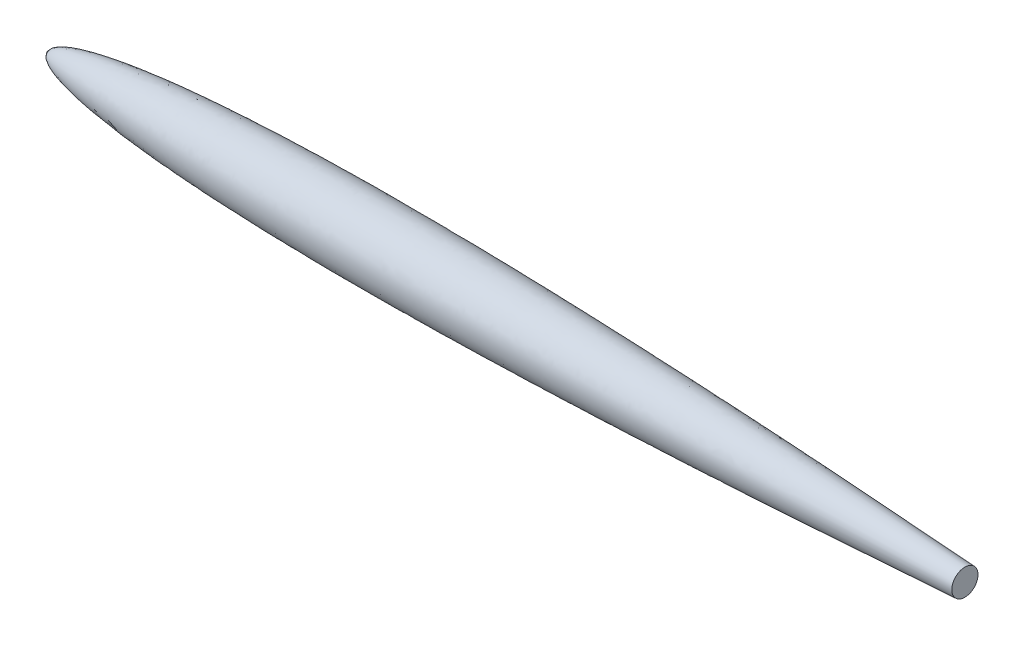
SolidWorks part; units mm, degrees
ref_plane "Front Plane" through (0, 0, 0) normal (0, 0, 1) x (1, 0, 0)
ref_plane "Top Plane" through (0, 0, 0) normal (0, 1, 0) x (1, 0, 0)
ref_plane "Right Plane" through (0, 0, 0) normal (1, 0, 0) x (0, 0, -1)
sketch "rootSketch" plane through (0, 0, 0) normal (0, 1, 0) x (1, 0, 0)
  line L0 (0, 0) -> (12000, 0) construction
  line L1 (2287.5, -274.5) -> (2287.5, 274.5) construction
  line L2 (0, 0) -> (9150, 0)
  spline S0 degree 4 poles (0, 0) (0.0002, 1.1783) (0.1019, 3.5275) (0.5605, 7.0328) (1.7549, 11.5943) (3.4354, 15.9) (5.4991, 19.934) (8.311, 24.4289) (11.4852, 28.5908) (14.9769, 32.5095) (19.9691, 37.4422) (26.9376, 43.4504) (36.0876, 50.0708) (47.4769, 57.0778) (61.5404, 64.6525) (77.1838, 72.0716) (94.7922, 79.4526) (114.338, 86.7678) (138.331, 94.9404) (167.4375, 103.839) (202.1902, 113.2976) (242.6189, 123.0791) (283.8524, 132.0744) (324.9149, 140.2471) (365.7664, 147.7384) (416.4511, 156.3658) (477.0221, 165.7669) (547.8456, 175.6689) (630.5882, 186.0011) (715.1014, 195.4737) (801.3628, 204.1819) (889.3556, 212.1992) (977.4135, 219.4631) (1065.524, 226.0562) (1153.6774, 232.0453) (1241.8663, 237.486) (1352.1845, 243.6614) (1484.6517, 250.1476) (1639.2816, 256.5129) (1816.0804, 262.345) (1992.9164, 266.8975) (2169.7779, 270.3041) (2346.6562, 272.6757) (2523.5444, 274.1064) (2744.6606, 274.8195) (3010.0013, 274.0955) (3319.5538, 271.2162) (3673.2968, 265.5239) (4026.9995, 257.745) (4380.6568, 248.1375) (4734.2663, 236.9143) (5087.8269, 224.2504) (5441.3385, 210.2884) (5794.8011, 195.1423) (6148.2151, 178.9004) (6501.5801, 161.6274) (6810.731, 145.6485) (7075.6854, 131.3482) (7296.4585, 119.0291) (7473.0634, 108.9317) (7649.6541, 98.5899) (7826.2302, 88.0006) (7980.7208, 78.5146) (8113.1314, 70.2227) (8223.4666, 63.2035) (8311.7306, 57.5217) (8399.99, 51.7724) (8488.2454, 45.9546) (8565.4639, 40.8032) (8631.6499, 36.3433) (8686.8001, 32.5972) (8730.924, 29.5818) (8775.0366, 26.5489) (8819.1658, 23.4963) (8863.2634, 20.4273) (8907.4107, 17.3359) (8951.4689, 14.232) (8990.1608, 11.4889) (9023.0969, 9.1423) (9050.9049, 7.1523) (9072.4988, 5.6029) (9095.4424, 3.9504) (9115.8352, 2.4783) (9143.0366, 0.5069) (9162.6518, -0.9192) (9195.0933, -3.2849) (9220.197, -5.1263) (9250.9065, -7.3837) (9278.2355, -9.4041) (9307.6056, -11.5815) (9335.7473, -13.6784) (9364.6143, -15.8368) (9393.0714, -17.9743) (9428.8949, -20.6757) (9471.7457, -23.9254) (9521.8197, -27.7492) (9578.9933, -32.1522) (9636.1916, -36.5945) (9693.3708, -41.0733) (9750.5568, -45.5912) (9807.7337, -50.1474) (9864.9111, -54.7434) (9922.083, -59.3791) (9979.2532, -64.0555) (10022.1272, -67.5936) (10050.7094, -69.9664) (10065, -71.1562) knots 0 0 0 0 0 0.000464 0.000929 0.001393 0.001858 0.002287 0.002716 0.003486 0.003922 0.004359 0.005488 0.007118 0.008378 0.009638 0.011797 0.013955 0.015919 0.017882 0.02181 0.025978 0.030146 0.034314 0.038482 0.042518 0.046554 0.054626 0.062698 0.07077 0.079497 0.088224 0.096952 0.105679 0.114406 0.123133 0.13186 0.140587 0.158059 0.17553 0.193002 0.210474 0.227946 0.245418 0.26289 0.280362 0.315306 0.35025 0.385194 0.420137 0.455081 0.490025 0.524969 0.559913 0.594857 0.6298 0.664744 0.699688 0.71716 0.734632 0.752104 0.769576 0.787048 0.80452 0.813256 0.821992 0.830728 0.839464 0.8482 0.856935 0.861303 0.865671 0.870039 0.874407 0.878775 0.883143 0.887511 0.891879 0.896247 0.898431 0.900615 0.902799 0.904983 0.907167 0.909351 0.912184 0.915017 0.91785 0.920682 0.923515 0.926348 0.929181 0.932013 0.934846 0.937679 0.943345 0.94901 0.954676 0.960341 0.966007 0.971672 0.977338 0.983003 0.988669 0.994334 1 1 1 1 1 construction
  spline S1 degree 4 poles (0, 0) (0.0002, 1.1783) (0.1019, 3.5275) (0.5605, 7.0328) (1.7549, 11.5943) (3.4354, 15.9) (5.4991, 19.934) (8.311, 24.4289) (11.4852, 28.5908) (14.9769, 32.5095) (19.9691, 37.4422) (26.9376, 43.4504) (36.0876, 50.0708) (47.4769, 57.0778) (61.5404, 64.6525) (77.1838, 72.0716) (94.7922, 79.4526) (114.338, 86.7678) (138.331, 94.9404) (167.4375, 103.839) (202.1902, 113.2976) (242.6189, 123.0791) (283.8524, 132.0744) (324.9149, 140.2471) (365.7664, 147.7384) (416.4511, 156.3658) (477.0221, 165.7669) (547.8456, 175.6689) (630.5882, 186.0011) (715.1014, 195.4737) (801.3628, 204.1819) (889.3556, 212.1992) (977.4135, 219.4631) (1065.524, 226.0562) (1153.6774, 232.0453) (1241.8663, 237.486) (1352.1845, 243.6614) (1484.6517, 250.1476) (1639.2816, 256.5129) (1816.0804, 262.345) (1992.9164, 266.8975) (2169.7779, 270.3041) (2346.6562, 272.6757) (2523.5444, 274.1064) (2744.6606, 274.8195) (3010.0013, 274.0955) (3319.5538, 271.2162) (3673.2968, 265.5239) (4026.9995, 257.745) (4380.6568, 248.1375) (4734.2663, 236.9143) (5087.8269, 224.2504) (5441.3385, 210.2884) (5794.8011, 195.1423) (6148.2151, 178.9004) (6501.5801, 161.6274) (6810.731, 145.6485) (7075.6854, 131.3482) (7296.4585, 119.0291) (7473.0634, 108.9317) (7649.6541, 98.5899) (7826.2302, 88.0006) (7980.7208, 78.5146) (8113.1314, 70.2227) (8223.4666, 63.2035) (8311.7306, 57.5217) (8399.99, 51.7724) (8488.2454, 45.9546) (8565.4639, 40.8032) (8631.6499, 36.3433) (8686.8001, 32.5972) (8730.924, 29.5818) (8775.0366, 26.5489) (8819.1658, 23.4963) (8863.2634, 20.4273) (8907.4107, 17.3359) (8951.4689, 14.232) (8990.1608, 11.4889) (9023.0969, 9.1423) (9050.9049, 7.1523) (9072.4988, 5.6029) (9095.4424, 3.9504) (9115.8352, 2.4783) (9134.8259, 1.1019) (9144.9864, 0.3644) (9150, 0) knots 0 0 0 0 0 0.000464 0.000929 0.001393 0.001858 0.002287 0.002716 0.003486 0.003922 0.004359 0.005488 0.007118 0.008378 0.009638 0.011797 0.013955 0.015919 0.017882 0.02181 0.025978 0.030146 0.034314 0.038482 0.042518 0.046554 0.054626 0.062698 0.07077 0.079497 0.088224 0.096952 0.105679 0.114406 0.123133 0.13186 0.140587 0.158059 0.17553 0.193002 0.210474 0.227946 0.245418 0.26289 0.280362 0.315306 0.35025 0.385194 0.420137 0.455081 0.490025 0.524969 0.559913 0.594857 0.6298 0.664744 0.699688 0.71716 0.734632 0.752104 0.769576 0.787048 0.80452 0.813256 0.821992 0.830728 0.839464 0.8482 0.856935 0.861303 0.865671 0.870039 0.874407 0.878775 0.883143 0.887511 0.891879 0.896247 0.898431 0.900615 0.902799 0.904983 0.907167 0.909351 0.909351 0.909351 0.909351 0.909351
  point P5 (2287.5, 0)
  dimension "rootQuarterChord" = 2287.5
  dimension "rootMaxThickness" = 549
revolve "Revolve1" add sketch "rootSketch" angle 360 about L0
ref_plane "Plane1" through (7503, 0, 0) normal (1, 0, 0) x (0, 0, -1)
sketch "cutSketch" plane through (7503, 0, 0) normal (1, 0, 0) x (0, 0, -1)
  circle A0 centre (0, 0) radius 274.5
  dimension "cutDiameter" = 549
extrude "Cut-Extrude1" cut sketch "cutSketch" along normal through all
equation "\"chord\" = 9.15"
equation "\"NACAairfoil\"= 0006"
equation "\"tailCutoffPercentage\"= 0.18"
equation "\"rootQuarterChord@rootSketch\"=\"chord\"/4"
equation "\"rootMaxThickness@rootSketch\"= \"rootQuarterChord@rootSketch\" * 4 * \"NACAairfoil\" / 100"
equation "\"cutDiameter@cutSketch\"=\"rootMaxThickness@rootSketch\""
equation "\"cutChord@Plane1\"= \"rootQuarterChord@rootSketch\" * 4 * ( 1 - \"tailCutoffPercentage\" )"
